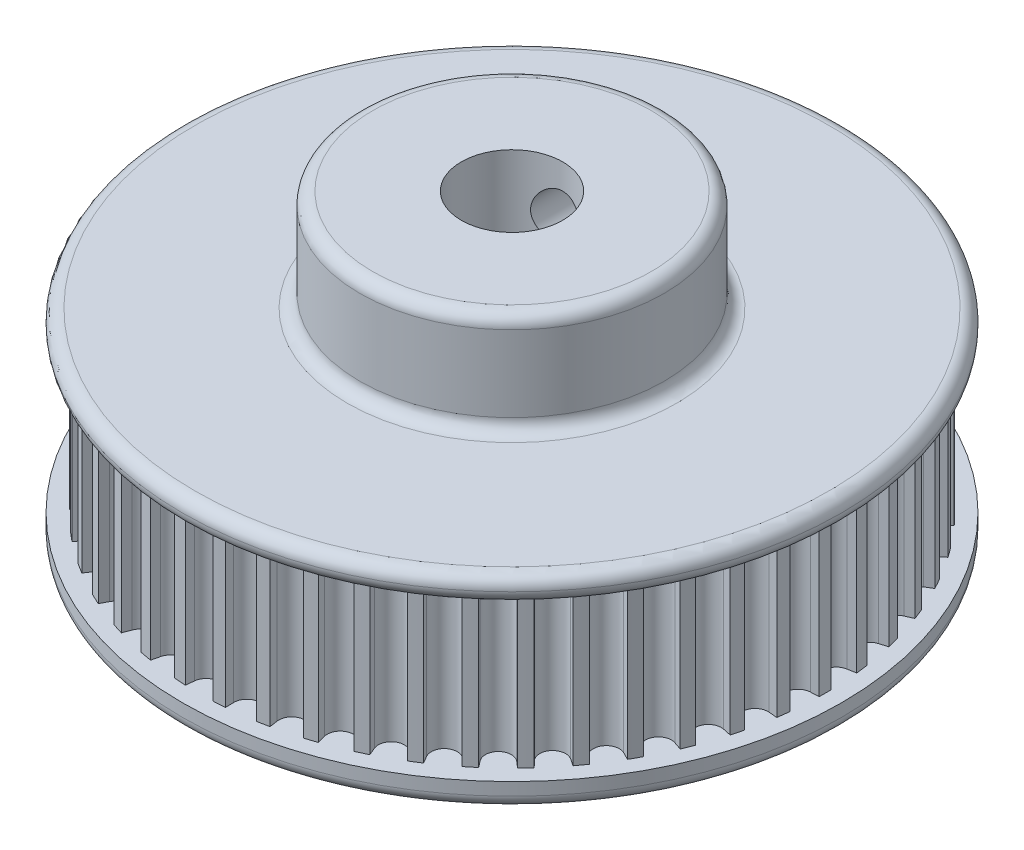
SolidWorks part; units mm, degrees
ref_plane "Front Plane" through (0, 0, 0) normal (0, 0, 1) x (1, 0, 0)
ref_plane "Top Plane" through (0, 0, 0) normal (0, 1, 0) x (1, 0, 0)
ref_plane "Right Plane" through (0, 0, 0) normal (1, 0, 0) x (0, 0, -1)
sketch "Sketch1" plane through (0, 0, 0) normal (0, 1, 0) x (1, 0, 0)
  line L3 (0, 0) -> (0, -38.3032) construction
  line L48 (1.6166, -38.1325) -> (1.7272, -39.1795)
  line L53 (-1.7272, -39.1795) -> (-1.6166, -38.1325)
  circle A0 centre (0, 0) radius 39.2176
  circle A1 centre (0, 0) radius 6.35
  arc A52 (1.6166, -38.1325) -> (-1.6166, -38.1325) centre (0, -38.3032) ccw
  point P6 (0, -36.6776)
  point P142 (0, 0)
  point P243 (0, 0)
  dimension "D1" = 3.4544
  dimension "D2" = 1.6256
  dimension "D4" = 78.4352
  dimension "D3" = 2.54
  dimension "D5" = 12.7
extrude "Boss-Extrude1" add sketch "Sketch1" along normal mid plane 19 contours A1 A52 L48 A0 L53 | L48 A52 L53 A0 region at (0, 0, 35.5686) region at (0, 0, 38.0968)
extrude "Cut-Extrude1" cut sketch "Sketch1<6>" against normal through all both and the other way through all contours L48 A52 L53 A0 region at (0, 0, 38.0968)
sketch "Sketch1<6>" plane through (0, 0, 0) normal (0, 1, 0) x (1, 0, 0) same geometry as "Sketch1"
pattern_circular "CirPattern1" count 50 over 360 about axis through (0, 9.5, 0) along (0, -1, 0) of "Cut-Extrude1" reverse direction yes
sketch "Sketch2" plane through (0, 9.5, 0) normal (0, 1, 0) x (1, 0, 0)
  circle A0 centre (0, 0) radius 41.275
  circle A1 centre (0, 0) radius 6.35 construction
  circle A2 centre (0, 0) radius 6.35
  dimension "D1" = 82.55
extrude "Boss-Extrude2" add sketch "Sketch2" along normal blind 3.175
mirror "Mirror2" about plane through (0, 0, 0) normal (0, 1, 0) of "Boss-Extrude2"
sketch "Sketch4" plane through (0, 12.675, 0) normal (0, 1, 0) x (1, 0, 0)
  circle A0 centre (0, 0) radius 19.05
  circle A1 centre (0, 0) radius 6.35 construction
  circle A2 centre (0, 0) radius 6.35
  dimension "D1" = 38.1
extrude "Boss-Extrude4" add sketch "Sketch4" along normal blind 12.7
sketch "Sketch5" plane through (0, 0, 0) normal (0, 0, 1) x (1, 0, 0)
  line L0 (0, 12.675) -> (0, 25.375) construction
  line L1 (41.275, 12.675) -> (-41.275, 12.675) construction
  line L2 (19.05, 25.375) -> (-19.05, 25.375) construction
  circle A0 centre (0, 19.025) radius 3.175
  point P2 (0, 0)
  dimension "D1" = 6.35
extrude "Cut-Extrude2" cut sketch "Sketch5" against normal up to next
fillet "Fillet2" radius 1.5875 5 edges at (0, -12.675, 41.275) (0, 9.5, 41.275) (0, 12.675, 41.275) (0, 25.375, 19.05) (0, 12.675, 19.05)
